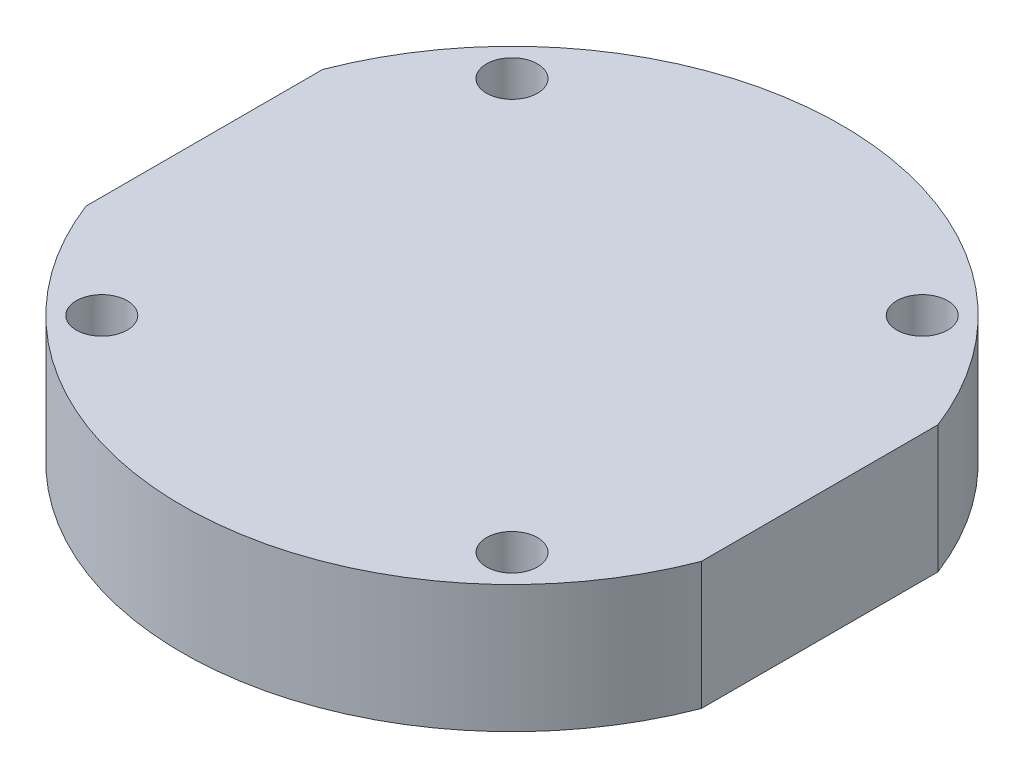
SolidWorks part; units mm, degrees
material "Copper"
ref_plane "Front Plane" through (0, 0, 0) normal (0, 0, 1) x (1, 0, 0)
ref_plane "Top Plane" through (0, 0, 0) normal (0, 1, 0) x (1, 0, 0)
ref_plane "Right Plane" through (0, 0, 0) normal (1, 0, 0) x (0, 0, -1)
ref_axis "Y Axis" through (0, 6.6675, 0) along (0, -1, 0)
sketch "outer" plane through (0, 0, 0) normal (0, 1, 0) x (1, 0, 0)
  circle A0 centre (0, 0) radius 19.05
  dimension "D1" = 38.1
extrude "Body" add sketch "outer" along normal blind 7.366
sketch "inner" plane through (0, 0, 0) normal (0, 1, 0) x (1, 0, 0)
  circle A0 centre (0, 0) radius 11.938
  dimension "D1" = 23.876
extrude "Pocket" cut sketch "inner" along normal blind 4.826
sketch "Screw Position" plane through (0, 0, 0) normal (0, 1, 0) x (1, 0, 0)
  point P0 (-11.8539, 11.8539)
  dimension "D1" = 16.764
hole_wizard "#4 Clearance Hole1" positions "Sketch7" profile "Sketch8" hole size "#4" standard "ANSI Inch" end condition through all
sketch "Sketch7" plane through (0, 7.366, 0) normal (0, 1, 0) x (1, 0, 0)
  point P0 (-11.8539, 11.8539)
sketch "Sketch8" plane through (-11.8539, 7.366, -11.8539) normal (1, 0, 0) x (0, 0, 1)
  line L0 (0, 0) -> (0, 7.366)
  line L1 (0, 7.366) -> (1.4732, 7.366)
  line L2 (1.4732, 7.366) -> (1.4732, 0)
  line L5 (1.4732, 0) -> (0, 0)
  line L11 (0, -6.35) -> (0, 107.95) construction
  dimension "Thru Hole Dia." = 2.9464
  dimension "Thru Hole Depth" = 7.366
pattern_circular "Screw Holes" count 4 over 360 about axis through (0, 6.6675, 0) along (0, -1, 0) of "#4 Clearance Hole1"
sketch "Post Sketch" plane through (0, 0, 0) normal (0, 1, 0) x (1, 0, 0)
  circle A0 centre (0, -5.334) radius 1
  circle A1 centre (5.334, -5.334) radius 1
  point P0 (0, -5.334)
  point P1 (5.334, -5.334)
  dimension "D3" = 2
  dimension "D4" = 2
  dimension "D1" = 5.334
extrude "Post" add sketch "Post Sketch" against normal blind 4.826 from surface starting at face at (0, 4.826, 11.938)
pattern_circular "CirPattern1" count 4 over 360 about axis through (0, 6.6675, 0) along (0, -1, 0) of "Post"
sketch "Flat Cut Sketch" plane through (0, 0, 0) normal (0, 1, 0) x (1, 0, 0)
  line L0 (0, 19.05) -> (0, -19.05) construction
  line L1 (-17.78, 19.05) -> (-20.32, -19.05) construction
  line L2 (17.78, -19.05) -> (20.32, -19.05)
  line L3 (17.78, -19.05) -> (17.78, 19.05)
  line L4 (17.78, 19.05) -> (20.32, 19.05)
  line L5 (20.32, -19.05) -> (20.32, 19.05)
  line L6 (17.78, -19.05) -> (20.32, 19.05) construction
  line L7 (17.78, 19.05) -> (20.32, -19.05) construction
  line L8 (-17.78, -19.05) -> (-20.32, 19.05) construction
  line L9 (-20.32, -19.05) -> (-20.32, 19.05)
  line L10 (-17.78, 19.05) -> (-20.32, 19.05)
  line L11 (-17.78, -19.05) -> (-17.78, 19.05)
  line L12 (-17.78, -19.05) -> (-20.32, -19.05)
  circle A0 centre (0, 0) radius 19.05 construction
  point P5 (19.05, 0)
  point P14 (-19.05, 0)
  dimension "D1" = 38.1
  dimension "D2" = 2.54
extrude "Flat Cut" cut sketch "Flat Cut Sketch" along normal through all
equation "\"outer_d\"= 3 / 2in"
equation "\"top_h\"= 1 / 4in"
equation "\"screw_r\"= 0.66in"
equation "\"inner_d\"= 0.94in"
equation "\"inner_h\"= 150mil"
equation "\"D1@outer\" = \"outer_d\""
equation "\"D1@Body\"=\"top_h\" + \"inset_h\""
equation "\"D1@inner\"=\"inner_d\""
equation "\"D1@Pocket\"=\"inner_h\" + \"inset_h\""
equation "\"D1@Screw Position\"=\"screw_r\""
equation "\"post_r1\"= 0.21in"
equation "\"post_r2\"= \"post_r1\" * sqr ( 2 )"
equation "\"post_bottom_h\"= 0.04in"
equation "\"D1@Post Sketch\" = \"post_r1\""
equation "\"D2@Post Sketch\" = \"post_r2\""
equation "\"post_d\"= 2mm"
equation "\"D3@Post Sketch\"=\"post_d\""
equation "\"D4@Post Sketch\"=\"post_d\""
equation "\"D1@Post\" = \"inner_h\" + \"post_bottom_h\""
equation "\"inset_h\"= 0.04in"
equation "\"D1@Flat Cut Sketch\" = \"outer_d\""
equation "\"flat_cut\" = 0.05in"
equation "\"D2@Flat Cut Sketch\" = \"flat_cut\" * 2"
